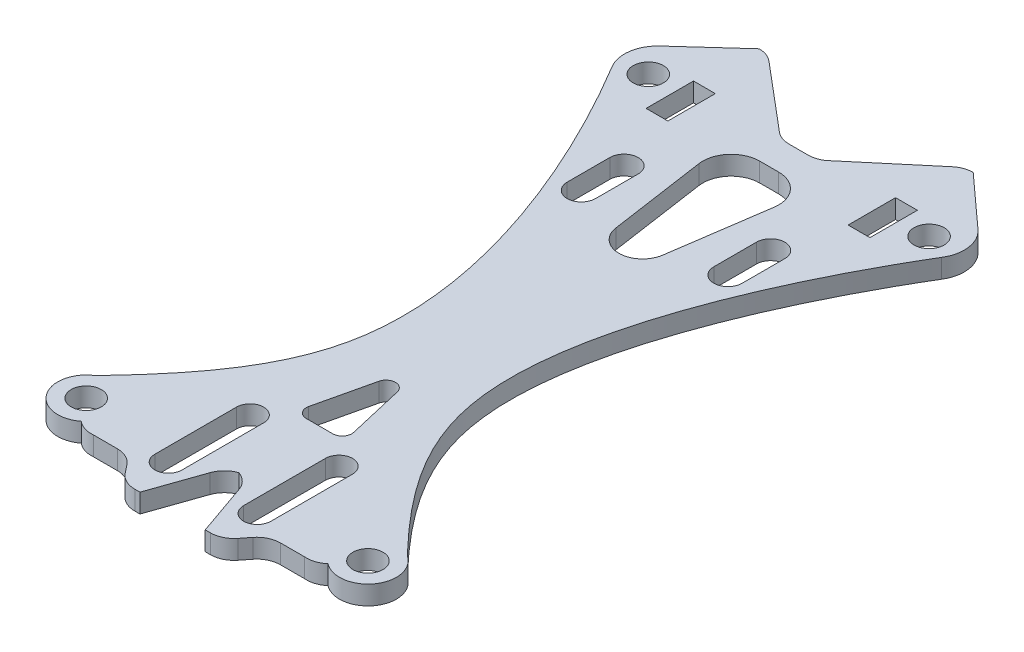
SolidWorks part; units mm, degrees
ref_plane "Alzado" through (0, 0, 0) normal (0, 0, 1) x (1, 0, 0)
ref_plane "Planta" through (0, 0, 0) normal (0, 1, 0) x (1, 0, 0)
ref_plane "Vista lateral" through (0, 0, 0) normal (1, 0, 0) x (0, 0, -1)
sketch "Croquis1" plane through (0, 0, 0) normal (0, 1, 0) x (1, 0, 0)
  line L0 (0, 0) -> (0, -2.5005) construction
  line L1 (-16.763, 33.4181) -> (-11.2867, 38.3871)
  line L2 (-3.6329, -113.0793) -> (172.3671, -113.0793) construction
  line L3 (16.763, 33.4181) -> (11.2867, 38.3871)
  line L6 (-1.0052, 31.2672) -> (-0.0407, 31.2672)
  line L13 (-11.1387, -31.9483) -> (-8.5987, -31.9483)
  line L14 (-6.6341, -32.9023) -> (-5.9532, -33.7675)
  line L15 (-3.9886, -34.7215) -> (-3.4412, -34.7215)
  line L16 (-3.4412, -34.7215) -> (-1.5339, -29.2621)
  line L17 (-4.6848, -21.8677) -> (-4.6848, -30.476) construction
  line L18 (-3.2497, -21.8677) -> (-3.2497, -30.476)
  line L19 (3.4412, -34.7215) -> (1.5339, -29.2621)
  line L20 (3.9886, -34.7215) -> (3.4412, -34.7215)
  line L21 (6.6341, -32.9023) -> (5.9532, -33.7675)
  line L22 (11.1387, -31.9483) -> (8.5987, -31.9483)
  line L27 (-1.3938, -19.2314) -> (1.3938, -19.2314)
  line L28 (1.0052, 31.2672) -> (0.0407, 31.2672)
  line L29 (2.7631, 31.9896) -> (9.66, 37.7992)
  line L30 (-2.7631, 31.9896) -> (-9.66, 37.7992)
  line L32 (-0.0407, 31.2672) -> (0.0407, 31.2672)
  line L33 (-6.1198, -21.8677) -> (-6.1198, -30.476)
  line L34 (-7.7286, 20.5928) -> (-7.7286, 16.0956) construction
  line L35 (-6.2293, 20.5928) -> (-6.2293, 16.0956)
  line L36 (-9.2279, 20.5928) -> (-9.2279, 16.0956)
  line L37 (4.6848, -21.8677) -> (4.6848, -30.476) construction
  line L38 (3.2497, -21.8677) -> (3.2497, -30.476)
  line L39 (6.1198, -21.8677) -> (6.1198, -30.476)
  line L40 (7.7286, 20.5928) -> (7.7286, 16.0956) construction
  line L41 (6.2293, 20.5928) -> (6.2293, 16.0956)
  line L42 (9.2279, 20.5928) -> (9.2279, 16.0956)
  line L43 (-0.9741, -12.0051) -> (-2.3679, -18.0051)
  line L46 (0.9741, -12.0051) -> (2.3679, -18.0051)
  line L47 (-1.0018, 28.1672) -> (1.0018, 28.1672)
  line L48 (3.9704, 24.7344) -> (2.4738, 14.4687)
  line L49 (-3.9704, 24.7344) -> (-2.4738, 14.4687)
  line L59 (-11.8, 31.9896) -> (-9.5, 31.9896)
  line L60 (-11.8, 31.9896) -> (-11.8, 26.9896)
  line L61 (-11.8, 26.9896) -> (-9.5, 26.9896)
  line L62 (-9.5, 31.9896) -> (-9.5, 26.9896)
  line L63 (11.8, 31.9896) -> (9.5, 31.9896)
  line L64 (11.8, 31.9896) -> (11.8, 26.9896)
  line L65 (9.5, 31.9896) -> (9.5, 26.9896)
  line L66 (11.8, 26.9896) -> (9.5, 26.9896)
  arc A9 (-2.7631, 31.9896) -> (-1.0052, 31.2672) centre (-1.0052, 33.7672) ccw
  arc A10 (0, -27.7272) -> (-1.5339, -29.2621) centre (0.8263, -30.0867) ccw
  arc A11 (-3.9886, -34.7215) -> (-5.9532, -33.7675) centre (-3.9886, -32.2215) cw
  arc A12 (-6.6341, -32.9023) -> (-8.5987, -31.9483) centre (-8.5987, -34.4483) ccw
  circle A13 centre (-14.85, -28.9795) radius 1.5875
  arc A14 (11.1387, -31.9483) -> (13.0022, -31.3429) centre (11.3598, -29.4581) ccw
  arc A15 (6.6341, -32.9023) -> (8.5987, -31.9483) centre (8.5987, -34.4483) cw
  arc A16 (3.9886, -34.7215) -> (5.9532, -33.7675) centre (3.9886, -32.2215) ccw
  arc A17 (0, -27.7272) -> (1.5339, -29.2621) centre (-0.8263, -30.0867) cw
  arc A18 (2.7631, 31.9896) -> (1.0052, 31.2672) centre (1.0052, 33.7672) cw
  arc A24 (-3.2497, -21.8677) -> (-6.1198, -21.8677) centre (-4.6848, -21.8677) ccw
  arc A25 (-6.1198, -30.476) -> (-3.2497, -30.476) centre (-4.6848, -30.476) ccw
  arc A26 (-6.2293, 20.5928) -> (-9.2279, 20.5928) centre (-7.7286, 20.5928) ccw
  arc A27 (-9.2279, 16.0956) -> (-6.2293, 16.0956) centre (-7.7286, 16.0956) ccw
  arc A28 (3.2497, -21.8677) -> (6.1198, -21.8677) centre (4.6848, -21.8677) cw
  arc A29 (6.1198, -30.476) -> (3.2497, -30.476) centre (4.6848, -30.476) cw
  arc A30 (6.2293, 20.5928) -> (9.2279, 20.5928) centre (7.7286, 20.5928) cw
  arc A31 (9.2279, 16.0956) -> (6.2293, 16.0956) centre (7.7286, 16.0956) cw
  arc A32 (0.9741, -12.0051) -> (-0.9741, -12.0051) centre (0, -12.2314) ccw
  arc A33 (1.3938, -19.2314) -> (2.3679, -18.0051) centre (1.3938, -18.2314) ccw
  arc A34 (-2.3679, -18.0051) -> (-1.3938, -19.2314) centre (-1.3938, -18.2314) ccw
  arc A35 (1.0018, 28.1672) -> (3.9704, 24.7344) centre (1.0018, 25.1672) cw
  arc A36 (-1.0018, 28.1672) -> (-3.9704, 24.7344) centre (-1.0018, 25.1672) ccw
  arc A37 (2.4738, 14.4687) -> (-2.4738, 14.4687) centre (0, 14.8294) cw
  arc A38 (-9.66, 37.7992) -> (-11.2867, 38.3871) centre (-11.2706, 35.8872) ccw
  arc A39 (-16.4682, -26.4534) -> (-13.0022, -31.3429) centre (-14.85, -28.9795) ccw
  arc A40 (9.66, 37.7992) -> (11.2867, 38.3871) centre (11.2706, 35.8872) cw
  circle A43 centre (14.85, -28.9795) radius 1.5875
  arc A45 (-11.1387, -31.9483) -> (-13.0022, -31.3429) centre (-11.3598, -29.4581) cw
  arc A48 (16.763, 33.4181) -> (17.3677, 28.953) centre (14.4111, 30.8261) cw
  circle A49 centre (-14.85, -28.9795) radius 3 construction
  arc A51 (-16.763, 33.4181) -> (-17.3677, 28.953) centre (-14.4111, 30.8261) ccw
  arc A54 (16.4682, -26.4534) -> (13.0022, -31.3429) centre (14.85, -28.9795) cw
  circle A55 centre (-14.8, 30.2239) radius 1.5875
  circle A56 centre (14.8, 30.2239) radius 1.5875
  spline S0 degree 3 poles (-16.4682, -26.4534) (-11.1181, -20.88) (0.4752, -5.2587) (-11.9823, 19.9928) (-17.3677, 28.953) knots 0 0 0 0 0.325398 1 1 1 1
  spline S1 degree 3 poles (16.4682, -26.4534) (11.1181, -20.88) (-0.4752, -5.2587) (11.9823, 19.9928) (17.3677, 28.953) knots 0 0 0 0 0.325398 1 1 1 1
  point P15 (-4.6848, -26.1719)
  point P27 (-12.05, 29.4649)
  point P52 (-7.7286, 18.3442)
  point P92 (4.6848, -26.1719)
  point P99 (7.7286, 18.3442)
  point P111 (0, -7.812)
  point P114 (2.6528, -19.2314)
  point P117 (-2.6528, -19.2314)
  point P123 (4.4709, 28.1672)
  point P126 (-4.4709, 28.1672)
  dimension "D4" = 2.5
  dimension "D5" = 3.175
  dimension "D6" = 2.5
  dimension "D7" = 2.5
  dimension "D8" = 1
  dimension "D10" = 3
  dimension "D11" = 2.5
  dimension "D2" = 7
  dimension "D3" = 3.175
  dimension "D14" = 6
  dimension "D12" = 14.8
  dimension "D9" = 6
  dimension "D13" = 2.3
  dimension "D15" = 5
  dimension "D16" = 14.85
  dimension "D17" = 9.5
extrude "Saliente-Extruir2" add sketch "Croquis1" along normal blind 2
